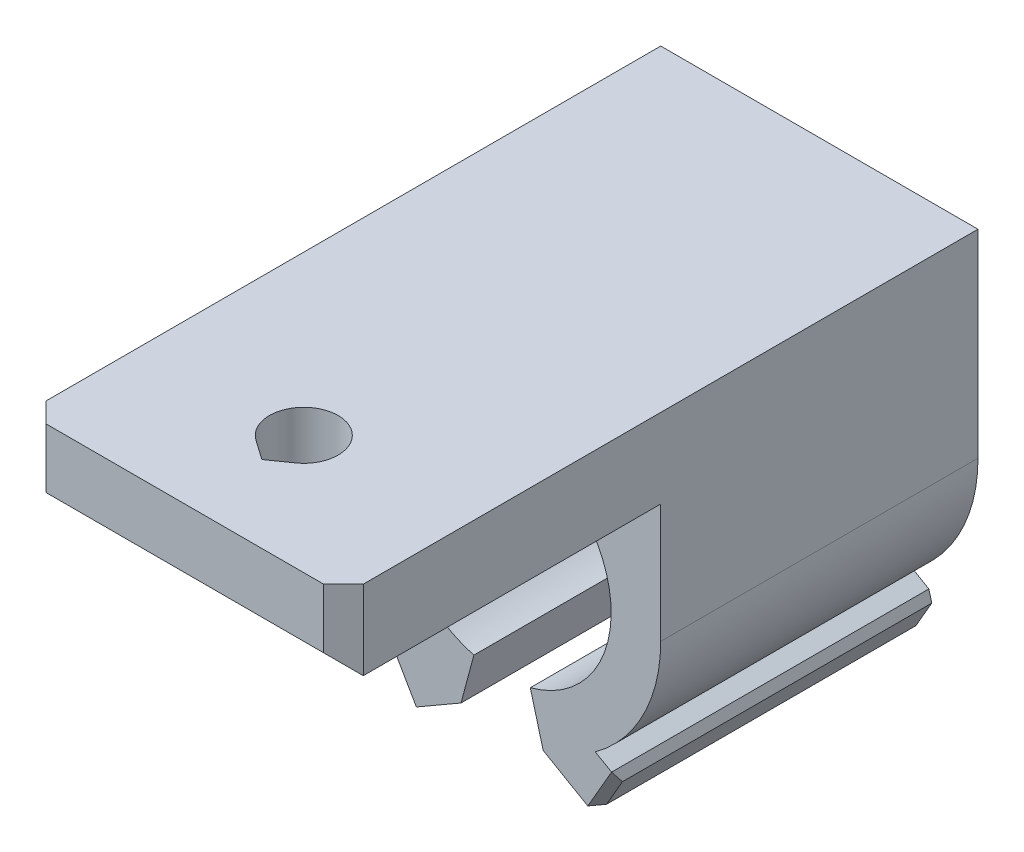
SolidWorks part; units mm, degrees
material "TPU"
ref_plane "X-Y Datum" through (0, 0, 0) normal (0, 0, 1) x (1, 0, 0)
ref_plane "X-Z Datum" through (0, 0, 0) normal (0, 1, 0) x (1, 0, 0)
ref_plane "Y-Z Datum" through (0, 0, 0) normal (1, 0, 0) x (0, 0, -1)
sketch "Sketch1" plane through (0, 0, 0) normal (0, 0, 1) x (1, 0, 0)
  line L0 (0, 10.16) -> (0, -10.16) construction
  line L1 (0, 0) -> (-2.6296, -9.8138)
  line L2 (0, 0) -> (2.6296, -9.8138)
  line L3 (-2.6296, -9.8138) -> (-5.9292, -11.7188)
  line L4 (-5.9292, -11.7188) -> (-7.4532, -9.0792)
  line L5 (-7.4532, -9.0792) -> (-5.9686, -8.222)
  line L6 (-10.16, 0) -> (10.16, 0) construction
  line L7 (2.6296, -9.8138) -> (5.9292, -11.7188)
  line L8 (5.9292, -11.7188) -> (7.4532, -9.0792)
  line L9 (7.4532, -9.0792) -> (5.9686, -8.222)
  line L10 (-10.16, 0) -> (-10.16, 12.7)
  line L11 (-10.16, 12.7) -> (10.16, 12.7)
  line L12 (10.16, 0) -> (10.16, 12.7)
  line L13 (10.16, 12.7) -> (10.16, 7.62)
  line L14 (-10.16, 12.7) -> (10.16, 12.7)
  line L15 (-10.16, 12.7) -> (-10.16, 7.62)
  line L16 (-10.16, 7.62) -> (10.16, 7.62)
  line L17 (0, 10.16) -> (0, 7.62)
  circle A0 centre (0, 0) radius 7.62 construction
  circle A1 centre (0, 0) radius 6.985
  circle A2 centre (0, 0) radius 10.16
  dimension "D1" = 15.24
  dimension "D2" = 13.97
  dimension "D3" = 20.32
  dimension "D4" = 15
  dimension "D5" = 30
  dimension "D6" = 3.81
  dimension "D7" = 3.048
  dimension "D8" = 20.32
  dimension "D9" = 12.7
extrude "clip" add sketch "Sketch1" along normal blind 20.32 contours A2 L16 L10 | A2 L16 L12 L14 | A2 L12 L16 | L16 A2 L17 | L17 A2 L16 | A2 L16 L1 A1 L2 | A2 L5 L4 L3 | A2 L7 L8 L9 region at (-2.4773, -8.2111, 0) region at (-5.3945, -9.8822, 0) region at (5.3945, -9.8822, 0) region at (-9.1669, 5.7855, 0) region at (9.1669, 5.7855, 0) region at (0, 10.6032, 0) region at (-2.5681, 8.6477, 0) region at (2.5681, 8.6477, 0)
extrude "back" add sketch "Sketch1<3>" along normal blind 40.64 contours L16 A2 L17 | L17 A2 L16 | A2 L16 L12 L11 L10 region at (0, 10.6032, 0) region at (-2.5681, 8.6477, 0) region at (2.5681, 8.6477, 0)
sketch "Sketch1<3>" plane through (0, 0, 0) normal (0, 0, 1) x (1, 0, 0) same geometry as "Sketch1"
sketch "Sketch4" plane through (0, 7.62, 0) normal (0, -1, 0) x (1, 0, 0)
  line L0 (-10.16, 40.64) -> (10.16, 40.64) construction
  line L1 (0, 40.64) -> (0, 20.32) construction
  line L2 (10.16, 20.32) -> (-10.16, 20.32) construction
  line L3 (-2.366, 36.399) -> (0, 38.0557)
  line L4 (-1.2619, 34.8221) -> (0, 35.7057)
  line L5 (1.2619, 34.8221) -> (0, 35.7057)
  line L6 (2.366, 36.399) -> (0, 38.0557)
  circle A0 centre (0, 33.02) radius 2.2
  circle A1 centre (0, 33.02) radius 4.125
  dimension "D1" = 4.4
  dimension "D3" = 55
  dimension "D4" = 8.25
  dimension "D2" = 7.62
  dimension "D5" = 55
extrude "hole" cut sketch "Sketch4" against normal through all contours A0 L1 | L1 A0 | L1 L4 A0 | L5 L1 A0 region at (0.3277, 7.62, 35.3283) region at (-0.3277, 7.62, 35.3283) region at (0.9337, 7.62, 33.02) region at (-0.9337, 7.62, 33.02)
extrude "counterbore" cut sketch "Sketch4<3>" against normal blind 1.397 contours L1 A1 A0 L4 | A1 L1 L5 A0 | L6 L1 A1 | L1 L3 A1 region at (0.6145, 7.62, 37.348) region at (-0.6145, 7.62, 37.348) region at (1.2127, 7.62, 36.8661) region at (-0.0922, 7.62, 36.4254)
sketch "Sketch4<3>" plane through (0, 7.62, 0) normal (0, -1, 0) x (1, 0, 0) same geometry as "Sketch4"
chamfer "Chamfer1" distance 1.27 angle 45 3 edges at (-10.16, 10.16, 40.64) (10.16, 10.16, 40.64) (0, 7.62, 40.64)
chamfer "Chamfer2" distance 0.508 angle 45 6 edges at (7.4532, -9.0792, 10.16) (5.9292, -11.7188, 10.16) (6.6912, -10.399, 20.32) (-7.4532, -9.0792, 10.16) (-5.9292, -11.7188, 10.16) (-6.6912, -10.399, 20.32)
